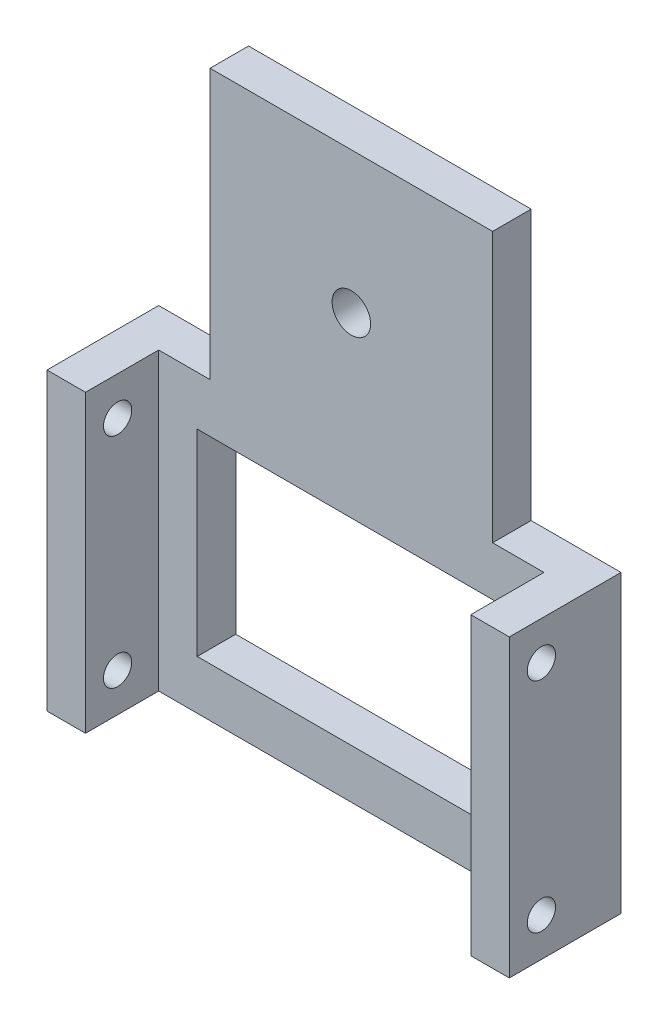
SolidWorks part; units mm, degrees
ref_plane "Front Plane" through (0, 0, 0) normal (0, 0, 1) x (1, 0, 0)
ref_plane "Top Plane" through (0, 0, 0) normal (0, 1, 0) x (1, 0, 0)
ref_plane "Right Plane" through (0, 0, 0) normal (1, 0, 0) x (0, 0, -1)
sketch "Sketch1" plane through (0, 0, 0) normal (0, 0, 1) x (1, 0, 0)
  line L0 (-11, 11.5) -> (-18, 11.5)
  line L1 (18, 11.5) -> (11, 11.5)
  line L2 (18, 11.5) -> (18, -11.5)
  line L3 (18, -11.5) -> (-18, -11.5)
  line L4 (-18, 11.5) -> (-18, -11.5)
  line L5 (18, 11.5) -> (-18, -11.5) construction
  line L6 (18, -11.5) -> (-18, 11.5) construction
  line L7 (-18, 11.5) -> (-15, 11.5)
  line L8 (-18, 11.5) -> (-18, -11.5)
  line L9 (-18, -11.5) -> (-15, -11.5)
  line L10 (-15, 11.5) -> (-15, -11.5)
  line L11 (18, 11.5) -> (15, 11.5)
  line L12 (18, 11.5) -> (18, -11.5)
  line L13 (18, -11.5) -> (15, -11.5)
  line L14 (15, 11.5) -> (15, -11.5)
  line L16 (-11, 11.5) -> (-11, 32.5)
  line L17 (-11, 32.5) -> (11, 32.5)
  line L18 (11, 11.5) -> (11, 32.5)
  line L20 (-12, 7.6667) -> (12, 7.6667)
  line L21 (-12, 7.6667) -> (-12, -7.6667)
  line L22 (-12, -7.6667) -> (12, -7.6667)
  line L23 (12, 7.6667) -> (12, -7.6667)
  line L24 (-12, 7.6667) -> (12, -7.6667) construction
  line L25 (-12, -7.6667) -> (12, 7.6667) construction
  circle A0 centre (0, 21.5) radius 1.5
  point P0 (0, 0)
  point P14 (0, -11.5)
  point P15 (0, 32.5)
  point P18 (0, 0)
  dimension "D10" = 3
  dimension "D1" = 30
  dimension "D2" = 3
  dimension "D3" = 3
  dimension "D4" = 22
  dimension "D5" = 23
  dimension "D6" = 10
  dimension "D7" = 11
  dimension "D8" = 6
extrude "Boss-Extrude1" add sketch "Sketch1" along normal blind 3 contours L1 L18 L17 L16 L0 L10 L3 L14 A0 region at (0, 12.8866, 0)
extrude "Boss-Extrude2" add sketch "Sketch1<4>" along normal blind 8.7 contours L1 L14 L3 L2 | L10 L0 L4 L3 region at (-16.5, 0, 0) region at (16.5, 0, 0)
sketch "Sketch1<4>" plane through (0, 0, 0) normal (0, 0, 1) x (1, 0, 0) same geometry as "Sketch1"
sketch "Sketch2" plane through (18, 0, 0) normal (1, 0, 0) x (0, 0, -1)
  line L0 (-8.7, 11.5) -> (0, 11.5) construction
  line L1 (-8.7, 11.5) -> (-8.7, -11.5) construction
  circle A0 centre (-6.2, 8.5) radius 1.1
  circle A1 centre (-6.2, -8.5) radius 1.1
  dimension "D1" = 2.2
  dimension "D2" = 3
  dimension "D3" = 2.5
  dimension "D4" = 17
extrude "Cut-Extrude1" cut sketch "Sketch2" against normal up to surface (36 mm away) up to face at (-18, 0, 4.35)
